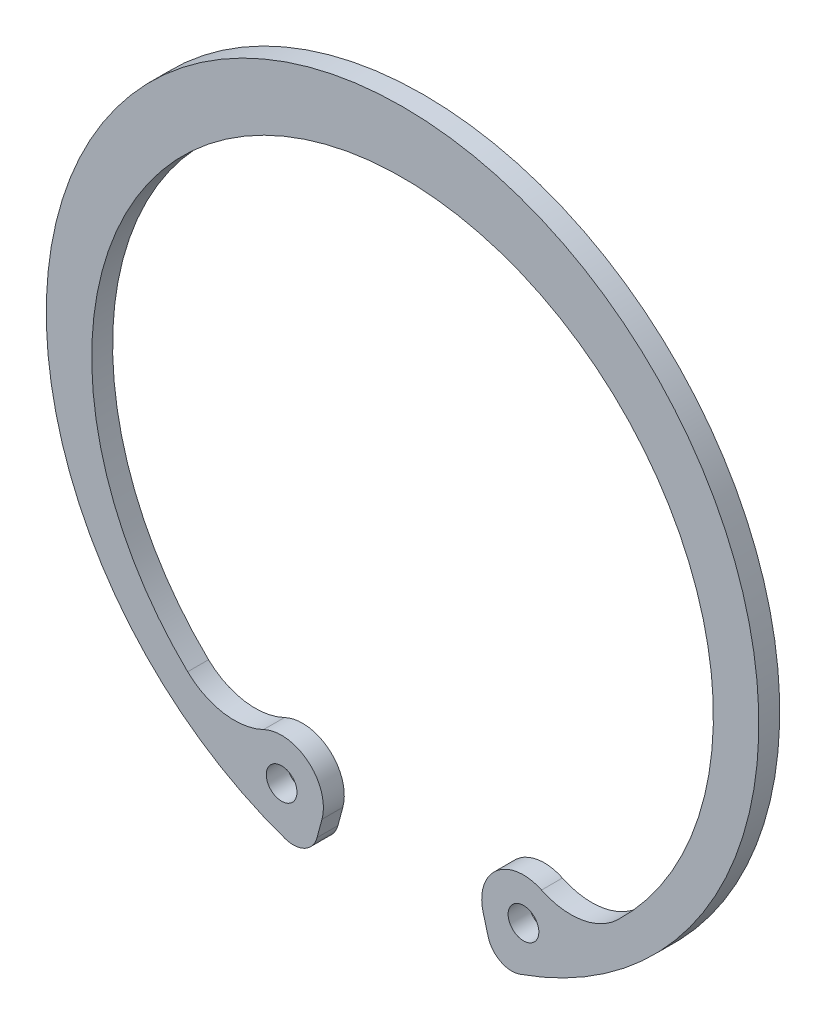
SolidWorks part; units mm, degrees
material "AISI 1020"
ref_plane "Спереди" through (0, 0, 0) normal (0, 0, 1) x (1, 0, 0)
ref_plane "Сверху" through (0, 0, 0) normal (0, 1, 0) x (1, 0, 0)
ref_plane "Справа" through (0, 0, 0) normal (1, 0, 0) x (0, 0, -1)
sketch "Эскиз1" plane through (0, 0, 0) normal (0, 0, 1) x (1, 0, 0)
  line L0 (0, -1000) -> (0, 49000) construction
  line L1 (0, 0) -> (11.4, -23.5898) construction
  line L2 (8.1726, -24.6594) -> (8.6599, -26.1298)
  line L3 (0, 24.6) -> (51.8, 24.6) construction
  arc A0 (11.3235, -27.3485) -> (0, 29.6) centre (0, 0) ccw
  circle A2 centre (11.4, -23.5898) radius 1.25
  arc A3 (12.6924, -20.445) -> (8.1726, -24.6594) centre (11.4, -23.5898) ccw
  arc A4 (12.6924, -20.445) -> (18.7686, -19.148) centre (14.783, -15.3579) ccw
  arc A5 (8.6599, -26.1298) -> (11.3235, -27.3485) centre (10.5584, -25.5006) ccw
  arc A6 (18.7686, -19.148) -> (0, 24.6) centre (0, -1.3) ccw
  dimension "_d2" = 59.2
  dimension "_d4" = 2.5
  dimension "_r1" = 5.5
  dimension "_r2" = 2
  dimension "D1" = 25.9
  dimension "_e" = 1.3
  dimension "_a" = 6.8
  dimension "_l" = 16
  dimension "_d3" = 51.8
sketch "Эскиз2" plane through (0, 0, 0) normal (0, 0, 1) x (1, 0, 0)
  line L0 (0, -201000) -> (0, 249000) construction
  line L1 (-6.9629, -26.0133) -> (-6.56, -24.5176)
  line L2 (8.1726, -24.6594) -> (8.6599, -26.1298) construction
  line L3 (0, 0) -> (11.3235, -27.3485) construction
  line L4 (0, 0) -> (-9.5529, -27.3814) construction
  line L5 (8.6599, -26.1298) -> (11.3235, -27.3485) construction
  line L6 (-9.5529, -27.3814) -> (-6.9629, -26.0133) construction
  line L7 (12.6924, -20.445) -> (8.1726, -24.6594) construction
  line L8 (-11.312, -20.567) -> (-6.56, -24.5176) construction
  line L9 (0, 29) -> (0, 30.7) construction
  circle A0 centre (0, 0) radius 29 construction
  circle A1 centre (0, 0) radius 27.5 construction
  circle A2 centre (0, 0) radius 20.2 construction
  arc A3 (0, 29) -> (-9.5529, -27.3814) centre (0, 0) ccw
  arc A4 (0, 24) -> (-17.4907, -19.5809) centre (0, -1.3003) ccw
  arc A5 (-9.5529, -27.3814) -> (-6.9629, -26.0133) centre (-8.8941, -25.4931) ccw
  arc A6 (-6.56, -24.5176) -> (-11.312, -20.567) centre (-9.8429, -23.6332) ccw
  arc A7 (8.6599, -26.1298) -> (11.3235, -27.3485) centre (10.5584, -25.5006) ccw construction
  arc A8 (12.6924, -20.445) -> (8.1726, -24.6594) centre (11.4, -23.5898) ccw construction
  arc A9 (-17.4907, -19.5809) -> (-11.312, -20.567) centre (-13.6884, -15.6069) ccw
  circle A10 centre (-9.8429, -23.6332) radius 1.25
  circle A11 centre (11.4, -23.5898) radius 1.25 construction
  arc A13 (12.6924, -20.445) -> (18.7686, -19.148) centre (14.783, -15.3579) ccw construction
  dimension "_D" = 55
  dimension "_d1" = 58
  dimension "_DD" = 40.4
  dimension "_b" = 5
  dimension "D1" = 157.508
  dimension "D2" = 29.6
  dimension "D3" = 160.767
  dimension "_s" = 1.7
sketch "Эскиз3" plane through (0, 0, 0) normal (0, 0, 1) x (1, 0, 0)
  line L0 (-6.9629, -26.0133) -> (-6.56, -24.5176) construction
  line L1 (-6.9629, -26.0133) -> (-6.56, -24.5176)
  line L2 (0, -1000) -> (0, 49000) construction
  line L3 (0, -1000.0733) -> (0, 48999.9267) construction
  line L4 (6.9629, -26.0133) -> (6.56, -24.5176)
  arc A0 (0, 24) -> (-17.4907, -19.5809) centre (0, -1.3003) ccw construction
  arc A1 (-17.4907, -19.5809) -> (-11.312, -20.567) centre (-13.6884, -15.6069) ccw construction
  arc A2 (-6.56, -24.5176) -> (-11.312, -20.567) centre (-9.8429, -23.6332) ccw construction
  arc A3 (-9.5529, -27.3814) -> (-6.9629, -26.0133) centre (-8.8941, -25.4931) ccw construction
  arc A4 (0, 29) -> (-9.5529, -27.3814) centre (0, 0) ccw construction
  arc A5 (17.4907, -19.5809) -> (-17.4907, -19.5809) centre (0, -1.3003) ccw
  arc A6 (-17.4907, -19.5809) -> (-11.312, -20.567) centre (-13.6884, -15.6069) ccw
  arc A7 (-6.56, -24.5176) -> (-11.312, -20.567) centre (-9.8429, -23.6332) ccw
  arc A8 (-9.5529, -27.3814) -> (-6.9629, -26.0133) centre (-8.8941, -25.4931) ccw
  arc A9 (9.5529, -27.3814) -> (-9.5529, -27.3814) centre (0, 0) ccw
  circle A10 centre (-9.8429, -23.6332) radius 1.25 construction
  circle A11 centre (-9.8429, -23.6332) radius 1.25
  circle A12 centre (9.8429, -23.6332) radius 1.25
  arc A13 (17.4907, -19.5809) -> (11.312, -20.567) centre (13.6884, -15.6069) cw
  arc A14 (6.56, -24.5176) -> (11.312, -20.567) centre (9.8429, -23.6332) cw
  arc A15 (9.5529, -27.3814) -> (6.9629, -26.0133) centre (8.8941, -25.4931) cw
extrude "Бобышка-Вытянуть1" add sketch "Эскиз3" along normal blind 1.7
equation "\"D1@Эскиз1\"=\"_d3@Эскиз1\"/2"
equation "\"D3@Эскиз2\"=(\"D2@Эскиз2\"*2*\"D1@Эскиз2\"/360)/(\"_d1@Эскиз2\"/360)"
equation "\"D1@Бобышка-Вытянуть1\"= \"_s@Эскиз2\""
